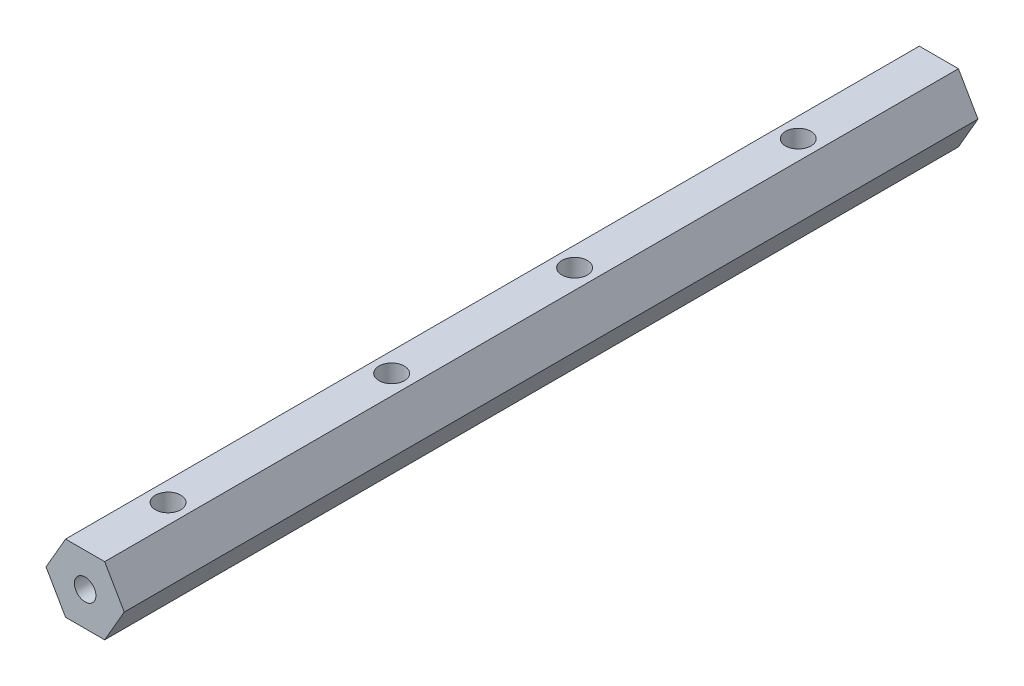
SolidWorks part; units mm, degrees
material "6061-T6 (SS)"
ref_plane "Front" through (0, 0, 0) normal (0, 0, 1) x (1, 0, 0)
ref_plane "Top" through (0, 0, 0) normal (0, 1, 0) x (1, 0, 0)
ref_plane "Right" through (0, 0, 0) normal (1, 0, 0) x (0, 0, -1)
sketch "Sketch1" plane through (0, 0, 0) normal (0, 0, 1) x (1, 0, 0)
  line L1 (7.3323, 0) -> (3.6662, 6.35)
  line L2 (3.6662, 6.35) -> (-3.6662, 6.35)
  line L3 (-3.6662, 6.35) -> (-7.3323, 0)
  line L4 (-7.3323, 0) -> (-3.6662, -6.35)
  line L5 (-3.6662, -6.35) -> (3.6662, -6.35)
  line L6 (3.6662, -6.35) -> (7.3323, 0)
  circle A0 centre (0, 0) radius 6.35 construction
  dimension "D1" = 12.7
extrude "Boss-Extrude1" add sketch "Sketch1" along normal blind 160.02
hole_wizard "#10-32 Tapped Hole1" positions "Sketch2" profile "Sketch4" tap size "#10-32" standard "ANSI Inch"
sketch "Sketch2" plane through (0, 0, 160.02) normal (0, 0, 1) x (1, 0, 0)
  point P0 (0, 0)
sketch "Sketch4" plane through (0, 0, 160.02) normal (1, 0, 0) x (0, -1, 0)
  line L0 (0, 0) -> (0, 77.4133)
  line L1 (0, 77.4133) -> (2.0193, 76.2)
  line L2 (2.0193, 76.2) -> (2.0193, 0)
  line L5 (2.0193, 0) -> (0, 0)
  line L10 (0, 77.4133) -> (-2.0193, 76.2) construction
  line L11 (0, -6.35) -> (0, 107.95) construction
  dimension "Tap Drill Dia." = 4.0386
  dimension "Tap Drill Depth" = 76.2
  dimension "Drill Angle" = 118
cosmetic thread "Hole Thread1" parameters "D1"=9.652, "D2"=4.826
sketch "Sketch5" plane through (0, 6.35, 0) normal (0, 1, 0) x (1, 0, 0)
  line L0 (3.6662, 0) -> (-3.6662, 0) construction
  circle A0 centre (0, -26.3652) radius 2.3813
  circle A1 centre (0, -68.2752) radius 2.3812
  circle A2 centre (0, -102.5652) radius 2.3812
  circle A3 centre (0, -144.4752) radius 2.3812
  dimension "D5" = 4.7625
  dimension "D1" = 26.3652
  dimension "D2" = 68.2752
  dimension "D3" = 102.5652
  dimension "D4" = 144.4752
extrude "Cut-Extrude1" cut sketch "Sketch5" against normal through all both and the other way through all
